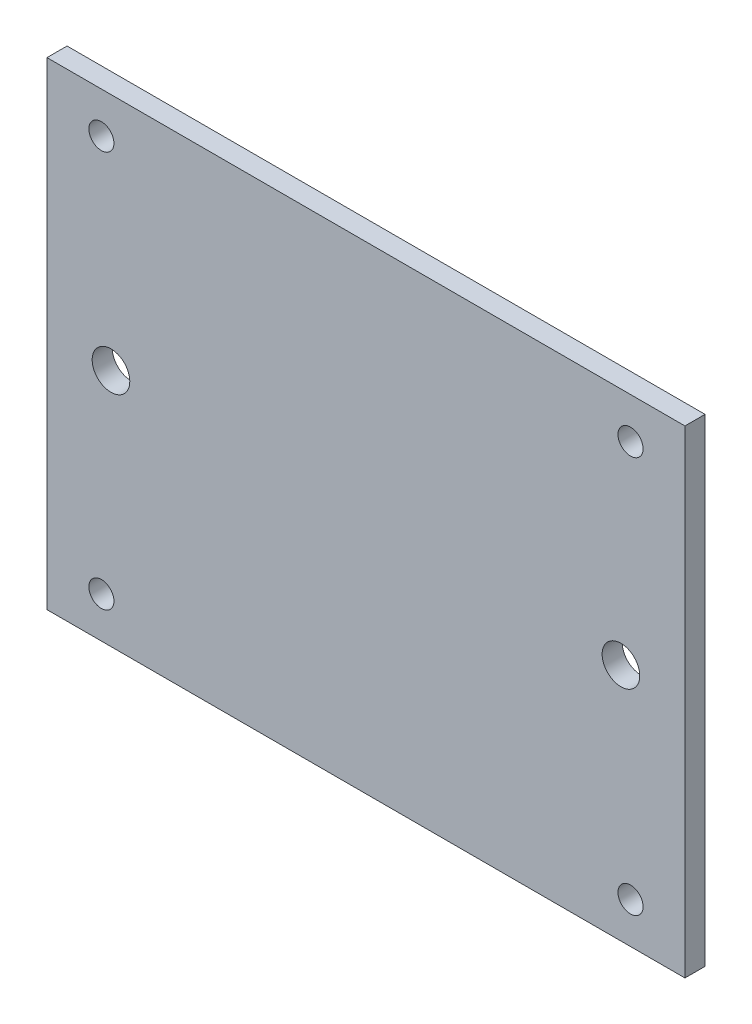
SolidWorks part; units mm, degrees
ref_plane "Front Plane" through (0, 0, 0) normal (0, 0, 1) x (1, 0, 0)
ref_plane "Top Plane" through (0, 0, 0) normal (0, 1, 0) x (1, 0, 0)
ref_plane "Right Plane" through (0, 0, 0) normal (1, 0, 0) x (0, 0, -1)
sketch "Sketch1" plane through (0, 0, 0) normal (0, 0, 1) x (1, 0, 0)
  line L0 (0, -40.427) -> (0, 40.427) construction
  line L1 (-25.42, -19.05) -> (25.42, -19.05)
  line L2 (-25.42, -19.05) -> (-25.42, 19.05)
  line L3 (-25.42, 19.05) -> (25.42, 19.05)
  line L4 (25.42, -19.05) -> (25.42, 19.05)
  line L5 (-25.42, -19.05) -> (25.42, 19.05) construction
  line L6 (-25.42, 19.05) -> (25.42, -19.05) construction
  line L7 (-52.9839, 0) -> (52.9839, 0) construction
  circle A2 centre (-21.0833, 15.8) radius 1
  circle A3 centre (21.0833, 15.8) radius 1
  circle A4 centre (21.0833, -15.8) radius 1
  circle A5 centre (-21.0833, -15.8) radius 1
  circle A6 centre (-20.32, 0) radius 1.5
  circle A7 centre (20.32, 0) radius 1.5
  point P0 (0, 0)
  point P9 (0, 0)
  point P14 (0, 0)
  dimension "D5" = 2
  dimension "D7" = 3
  dimension "D8" = 5.1
  dimension "D1" = 50.84
  dimension "D2" = 38.1
  dimension "D6" = 3.25
extrude "Boss-Extrude1" add sketch "Sketch1" along normal blind 1.6
